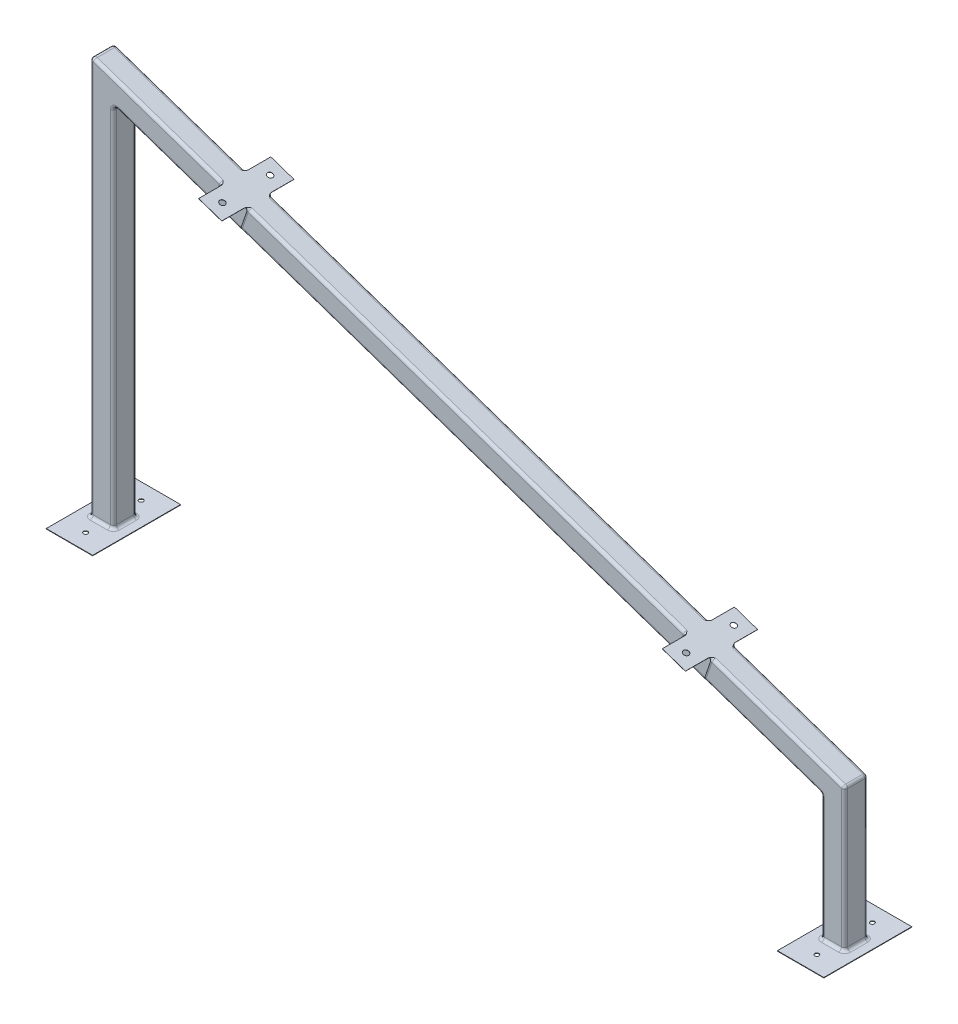
SolidWorks part; units mm, degrees
ref_plane "Alzado" through (0, 0, 0) normal (0, 0, 1) x (1, 0, 0)
ref_plane "Planta" through (0, 0, 0) normal (0, 1, 0) x (1, 0, 0)
ref_plane "Vista lateral" through (0, 0, 0) normal (1, 0, 0) x (0, 0, -1)
sketch "Croquis1" plane through (0, 0, 0) normal (0, 0, 1) x (1, 0, 0)
  line L0 (19.05, 0) -> (19.05, 600.7623)
  line L1 (19.05, 600.7623) -> (1178.0763, 205.7334)
  line L2 (1178.0763, 205.7334) -> (1178.0763, 0)
  line L3 (1178.0763, 0) -> (1216.1763, 0)
  line L4 (1216.1763, 0) -> (1216.1763, 233)
  line L5 (1216.1763, 233) -> (-19.05, 654)
  line L6 (-19.05, 654) -> (-19.05, 0)
  line L7 (-19.05, 0) -> (19.05, 0)
  point P10 (0, 0)
  dimension "D1" = 654
  dimension "D2" = 233
  dimension "D3" = 1305
  dimension "D4" = 38.1
  dimension "D5" = 38.1
extrude "Saliente-Extruir1" add sketch "Croquis1" along normal mid plane 38.1
sketch "Croquis3" plane through (0, 0, 0) normal (0, -1, 0) x (1, 0, 0)
  line L0 (1197.1263, 19.05) -> (1197.1263, 72) construction
  line L1 (38, -72) -> (-38, -72)
  line L2 (38, -72) -> (38, 72)
  line L3 (38, 72) -> (-38, 72)
  line L4 (-38, -72) -> (-38, 72)
  line L5 (38, -72) -> (-38, 72) construction
  line L6 (38, 72) -> (-38, -72) construction
  line L7 (1178.0763, 19.05) -> (1178.0763, -19.05) construction
  line L8 (1178.0763, 0) -> (1216.1763, 0) construction
  line L9 (1216.1763, 19.05) -> (1216.1763, -19.05) construction
  line L10 (0, 19.05) -> (0, 72) construction
  line L11 (1159.1263, -72) -> (1235.1263, -72)
  line L12 (1159.1263, -72) -> (1159.1263, 72)
  line L13 (1159.1263, 72) -> (1235.1263, 72)
  line L14 (1235.1263, -72) -> (1235.1263, 72)
  line L15 (1159.1263, -72) -> (1235.1263, 72) construction
  line L16 (1159.1263, 72) -> (1235.1263, -72) construction
  line L17 (-19.05, 19.05) -> (19.05, 19.05) construction
  line L18 (0, -19.05) -> (0, -72) construction
  line L19 (-19.05, -19.05) -> (19.05, -19.05) construction
  line L20 (1178.0763, 19.05) -> (1216.1763, 19.05) construction
  line L21 (1197.1263, -19.05) -> (1197.1263, -72) construction
  line L22 (1178.0763, -19.05) -> (1216.1763, -19.05) construction
  circle A0 centre (0, 45.525) radius 3.5
  circle A1 centre (0, -45.525) radius 3.5
  circle A2 centre (1197.1263, 45.525) radius 3.5
  circle A3 centre (1197.1263, -45.525) radius 3.5
  point P0 (0, 0)
  point P10 (1197.1263, 0)
  dimension "D3" = 7
  dimension "D1" = 76
  dimension "D2" = 144
extrude "Saliente-Extruir2" add sketch "Croquis3" along normal blind 0.75
sketch "Croquis5" plane through (197.7207, 580.1184, 0) normal (0.3226, 0.9465, 0) x (0.9465, -0.3226, 0)
  line L0 (0.9846, 19.05) -> (0.9846, 59.05)
  line L1 (1075.9846, 19.05) -> (-229.0154, 19.05) construction
  line L2 (0.9846, 59.05) -> (40.9846, 59.05)
  line L3 (40.9846, 59.05) -> (40.9846, 19.05)
  line L4 (0.9846, -19.05) -> (0.9846, -59.05)
  line L5 (1075.9846, -19.05) -> (-229.0154, -19.05) construction
  line L6 (0.9846, -59.05) -> (40.9846, -59.05)
  line L7 (40.9846, -59.05) -> (40.9846, -19.05)
  line L8 (802.9846, 19.05) -> (802.9846, 59.05)
  line L9 (802.9846, 59.05) -> (842.9846, 59.05)
  line L10 (842.9846, 59.05) -> (842.9846, 19.05)
  line L11 (802.9846, -19.05) -> (802.9846, -59.05)
  line L12 (802.9846, -59.05) -> (842.9846, -59.05)
  line L13 (842.9846, -59.05) -> (842.9846, -19.05)
  line L14 (-229.0154, -19.05) -> (-229.0154, 19.05) construction
  line L16 (0.9846, 19.05) -> (40.9846, 19.05)
  line L17 (0.9846, -19.05) -> (40.9846, -19.05)
  line L18 (842.9846, 19.05) -> (802.9846, 19.05)
  line L19 (802.9846, -19.05) -> (842.9846, -19.05)
  line L20 (822.9846, 59.05) -> (822.9846, 19.05) construction
  line L21 (822.9846, -19.05) -> (822.9846, -59.05) construction
  line L22 (20.9846, 19.05) -> (20.9846, 59.05) construction
  line L23 (20.9846, -19.05) -> (20.9846, -59.05) construction
  circle A0 centre (20.9846, 39.05) radius 4.5
  circle A1 centre (20.9846, -39.05) radius 4.5
  circle A2 centre (822.9846, 39.05) radius 4.5
  circle A3 centre (822.9846, -39.05) radius 4.5
  dimension "D5" = 9
  dimension "D1" = 230
  dimension "D2" = 40
  dimension "D3" = 40
  dimension "D4" = 762
extrude "Saliente-Extruir3" add sketch "Croquis5" against normal blind 38.1
sketch "Croquis6" plane through (797.9132, -271.9514, 0) normal (0.9465, -0.3226, 0) x (0, 0, -1)
  line L0 (-19.42, 574.7873) -> (-19.42, 612.5173)
  line L1 (-59.05, 574.7873) -> (-19.05, 574.7873) construction
  line L2 (-19.42, 612.5173) -> (-59.05, 612.5173)
  line L3 (-59.05, 574.7873) -> (-59.05, 612.8873) construction
  line L4 (-59.05, 612.5173) -> (-59.05, 574.7873)
  line L5 (-59.05, 574.7873) -> (-19.42, 574.7873)
  line L6 (-59.05, 612.8873) -> (-19.05, 612.8873) construction
  line L7 (-19.05, 392.345) -> (-19.05, 612.8873) construction
  line L8 (19.42, 574.7873) -> (19.42, 612.5173)
  line L9 (19.05, 574.7873) -> (59.05, 574.7873) construction
  line L10 (19.42, 612.5173) -> (59.05, 612.5173)
  line L11 (59.05, 574.7873) -> (59.05, 612.8873) construction
  line L12 (59.05, 612.5173) -> (59.05, 574.7873)
  line L13 (59.05, 574.7873) -> (19.42, 574.7873)
  line L14 (19.42, 574.7873) -> (19.1933, 574.1778)
  line L15 (19.05, 612.8873) -> (59.05, 612.8873) construction
  line L16 (19.05, 574.7873) -> (19.05, 612.8873) construction
  line M7 (19.05, 574.7873) -> (59.05, 574.7873)
  line M8 (59.05, 574.7873) -> (59.05, 612.8873)
  dimension "D1" = 0.37
  dimension "D2" = 0.37
  dimension "D3" = 0.37
  dimension "D4" = 0.37
extrude "Cortar-Extruir1" cut sketch "Croquis6" against normal through all contours L4 L5 L0 L2 | L10 L8 M7 M8 region at (989.4287, 289.9605, 39.235) region at (989.4287, 289.9605, -39.235)
fillet "Redondeo1" radius 5 24 edges at (102.7057, 572.2501, 19.05) (89.8014, 616.9004, 19.05) (1178.0763, 205.7334, 0) (19.05, 600.7623, 0) (-19.05, 654, 0) (-19.05, 327, -19.05) (89.8014, 616.9004, -19.05) (102.7057, 572.2501, -19.05) (584.8521, 407.921, -19.05) (1216.1763, 233, 0) (1080.7095, 238.9188, -19.05) (1178.0763, 102.8667, -19.05) (1178.0763, 102.8667, 19.05) (1216.1763, 116.5, 19.05) (1216.1763, 116.5, -19.05) (1105.9051, 270.5835, -19.05) (1105.9051, 270.5835, 19.05) (1080.7095, 238.9188, 19.05) (584.8521, 407.921, 19.05) (597.1433, 443.9839, -19.05) (597.1433, 443.9839, 19.05) (-19.05, 327, 19.05) (19.05, 300.3812, -19.05) (19.05, 300.3812, 19.05)
fillet "Redondeo2" radius 5 32 edges at (1214.7118, 0, -17.5855) (1197.1263, 0, -19.05) (1179.5408, 0, -17.5855) (1178.0763, 0, 0) (1179.5408, 0, 17.5855) (1216.1763, 0, 0) (1214.7118, 0, 17.5855) (1197.1263, 0, 19.05) (198.1803, 578.4146, 17.5855) (186.8339, 545.124, 17.5855) (224.6952, 532.2198, 17.5855) (236.0416, 565.5104, 17.5855) (17.5855, 0, -17.5855) (-17.5855, 0, 17.5855) (-19.05, 0, 0) (-17.5855, 0, -17.5855) (0, 0, -19.05) (19.05, 0, 0) (17.5855, 0, 17.5855) (0, 0, 19.05) (995.1615, 306.7809, -17.5855) (983.8152, 273.4903, -17.5855) (945.9538, 286.3945, -17.5855) (957.3002, 319.6851, -17.5855) (945.9538, 286.3945, 17.5855) (957.3002, 319.6851, 17.5855) (983.8152, 273.4903, 17.5855) (995.1615, 306.7809, 17.5855) (224.6952, 532.2198, -17.5855) (236.0416, 565.5104, -17.5855) (186.8339, 545.124, -17.5855) (198.1803, 578.4146, -17.5855)
fillet "Redondeo3" radius 5 4 edges at (205.2921, 537.2857, 19.42) (964.412, 278.5562, 19.42) (964.412, 278.5562, -19.42) (205.2921, 537.2857, -19.42)
